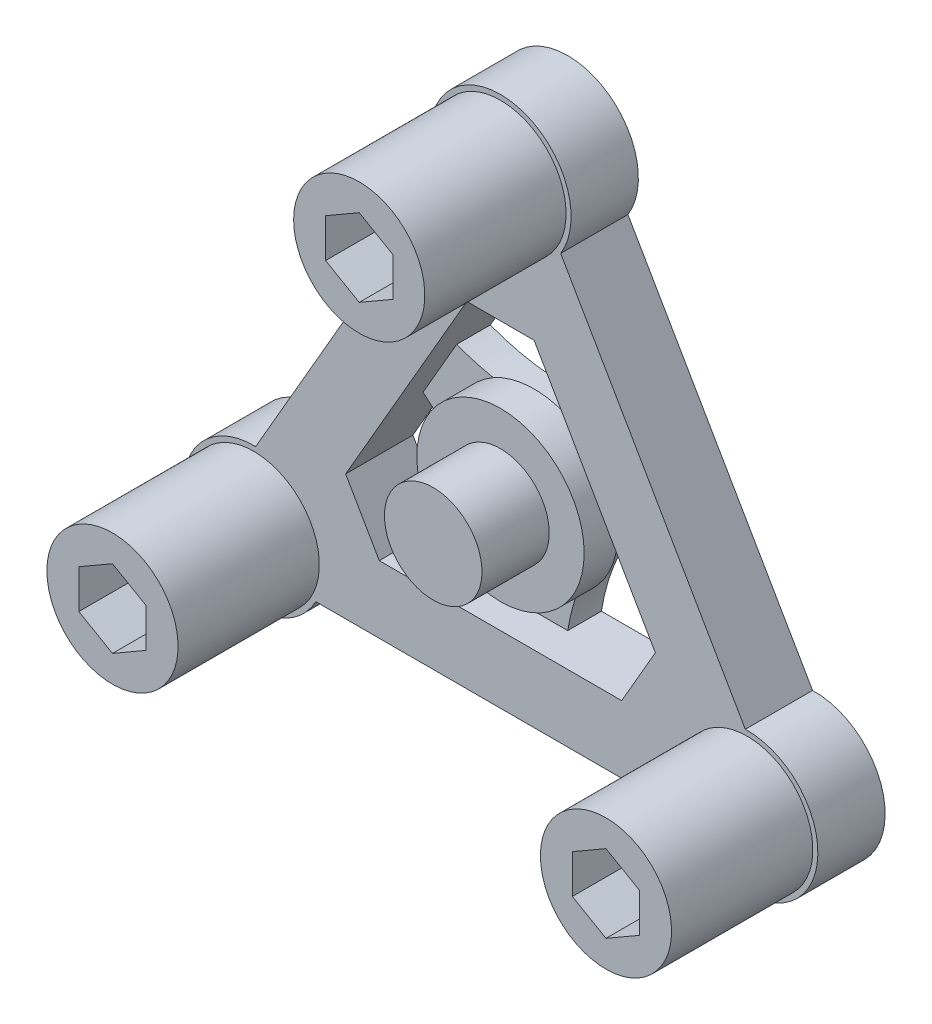
SolidWorks part; units mm, degrees
note: The reader was unsure of these and kept them because the rebuilt part matched: shared geometry of "Sketch5<3>".
ref_plane "Front Plane" through (0, 0, 0) normal (0, 0, 1) x (1, 0, 0)
ref_plane "Top Plane" through (0, 0, 0) normal (0, 1, 0) x (1, 0, 0)
ref_plane "Right Plane" through (0, 0, 0) normal (1, 0, 0) x (0, 0, -1)
sketch "Sketch1" plane through (0, 0, 0) normal (0, 0, 1) x (1, 0, 0)
  line L0 (0, 21.1785) -> (0, 0) construction
  line L1 (0, 0) -> (18.3411, -10.5892) construction
  line L2 (0, 0) -> (-18.3411, -10.5892) construction
  line L3 (0, 21.1785) -> (0, 42.357) construction
  line L4 (0, -55) -> (0, 55) construction
  line L5 (18.3411, -10.5892) -> (36.6822, -21.1785) construction
  line L6 (-18.3411, -10.5892) -> (-36.6822, -21.1785) construction
  circle A0 centre (0, 0) radius 21.1785 construction
  circle A1 centre (0, 42.357) radius 21.1785 construction
  circle A2 centre (36.6822, -21.1785) radius 21.1785 construction
  circle A3 centre (-36.6822, -21.1785) radius 21.1785 construction
  dimension "D3" = 42.357
  dimension "D4" = 42.357
  dimension "D1" = 120
  dimension "D2" = 120
sketch "Sketch2" plane through (0, 0, 0) normal (0, 0, 1) x (1, 0, 0)
  line L0 (-36.6822, -21.1785) -> (0, 42.357) construction
  line L1 (0, 42.357) -> (36.6822, -21.1785) construction
  line L2 (36.6822, -21.1785) -> (-36.6822, -21.1785) construction
  line L4 (-45.3425, -26.1785) -> (0, 52.357)
  line L7 (0, 32.357) -> (-28.022, -16.1785)
  line L8 (0, 21.1785) -> (0, 42.357) construction
  line L9 (0, 32.357) -> (28.022, -16.1785)
  line L10 (18.3411, -10.5892) -> (36.6822, -21.1785) construction
  line L11 (28.022, -16.1785) -> (-28.022, -16.1785)
  line L12 (-18.3411, -10.5892) -> (-36.6822, -21.1785) construction
  line L13 (0, -55) -> (0, 55) construction
  line L14 (0, 52.357) -> (45.3425, -26.1785)
  line L15 (45.3425, -26.1785) -> (-45.3425, -26.1785)
  line L16 (-22.6712, 13.0893) -> (-14.011, 8.0893) construction
  circle A3 centre (0, 42.357) radius 10.5
  circle A4 centre (36.6822, -21.1785) radius 10.5
  circle A5 centre (-36.6822, -21.1785) radius 10.5
  point P23 (-18.3411, 10.5893)
  point P24 (-18.3411, 10.5893)
  dimension "D2" = 21
  dimension "D1" = 10
extrude "Boss-Extrude1" add sketch "Sketch2" along normal mid plane 10 contours L4 A5 L15 | L14 A3 L4 | L15 A4 L14 | L9 A4 L11 | L11 A5 L7 | L7 A3 L9
sketch "Sketch3" plane through (0, 0, 0) normal (0, 0, 1) x (1, 0, 0)
  line L0 (-14.011, 8.0893) -> (0, 0) construction
  line L1 (28.022, -16.1785) -> (-28.022, -16.1785) construction
  line L2 (0, 0) -> (0, -16.1785) construction
  line L4 (0, 0) -> (14.011, 8.0893) construction
  line L6 (-16.511, 3.7591) -> (-11.511, 12.4194)
  line L7 (11.511, 12.4194) -> (16.511, 3.7591)
  line L8 (-5, -16.1785) -> (5, -16.1785)
  line L9 (0, 32.357) -> (28.022, -16.1785) construction
  line L10 (0, 32.357) -> (-28.022, -16.1785) construction
  arc A0 (-16.511, 3.7591) -> (-5, -16.1785) centre (-36.6822, -21.1785) cw
  arc A1 (5, -16.1785) -> (16.511, 3.7591) centre (36.6822, -21.1785) cw
  arc A2 (-11.511, 12.4194) -> (11.511, 12.4194) centre (0, 42.357) ccw
  point P14 (-14.011, 8.0893)
  point P17 (14.011, 8.0893)
  point P20 (0, -16.1785)
  dimension "D1" = 10
extrude "Boss-Extrude2" add sketch "Sketch3" against normal up to surface (5 mm away) up to face at (0, 0, -5)
sketch "Sketch4" plane through (0, 0, 5) normal (0, 0, 1) x (1, 0, 0)
  circle A0 centre (-36.6822, -21.1785) radius 9.75
  circle A1 centre (36.6822, -21.1785) radius 9.75
  circle A2 centre (0, 42.357) radius 9.75
  dimension "D1" = 19.5
extrude "Boss-Extrude3" add sketch "Sketch4" along normal blind 21
sketch "Sketch5" plane through (0, 0, 0) normal (0, 0, 1) x (1, 0, 0)
  circle A0 centre (0, 0) radius 7.25
  circle A1 centre (0, 0) radius 12.4416
  dimension "D1" = 14.5
extrude "Boss-Extrude4" add sketch "Sketch5" along normal up to surface (5 mm away) contours A1 up to face at (9.75, 42.357, 5)
extrude "Boss-Extrude5" add sketch "Sketch5<3>" along normal offset from surface (15 mm away) 10 contours A0 up to face at (12.4416, 0, 5) offset beyond the face yes
sketch "Sketch5<3>" plane through (0, 0, 0) normal (0, 0, 1) x (1, 0, 0) same geometry as "Sketch5"
chamfer "Chamfer1" distance 10 3 edges at (0, 32.357, 0) (-28.022, -16.1785, 0) (28.022, -16.1785, 0)
sketch "Sketch8" plane through (0, 0, 26) normal (0, 0, 1) x (1, 0, 0)
  line L1 (-41.6822, -24.0653) -> (-36.6822, -26.952)
  line L2 (-36.6822, -26.952) -> (-31.6822, -24.0653)
  line L3 (-31.6822, -24.0653) -> (-31.6822, -18.2917)
  line L4 (-31.6822, -18.2917) -> (-36.6822, -15.405)
  line L5 (-36.6822, -15.405) -> (-41.6822, -18.2917)
  line L6 (-41.6822, -18.2917) -> (-41.6822, -24.0653)
  line L7 (41.6822, -24.0653) -> (41.6822, -18.2917)
  line L8 (41.6822, -18.2917) -> (36.6822, -15.405)
  line L9 (36.6822, -15.405) -> (31.6822, -18.2917)
  line L10 (31.6822, -18.2917) -> (31.6822, -24.0653)
  line L11 (31.6822, -24.0653) -> (36.6822, -26.952)
  line L12 (36.6822, -26.952) -> (41.6822, -24.0653)
  line L13 (0, 48.1305) -> (-5, 45.2438)
  line L14 (-5, 45.2438) -> (-5, 39.4702)
  line L15 (-5, 39.4702) -> (0, 36.5835)
  line L16 (0, 36.5835) -> (5, 39.4702)
  line L17 (5, 39.4702) -> (5, 45.2438)
  line L18 (5, 45.2438) -> (0, 48.1305)
  circle A0 centre (-36.6822, -21.1785) radius 5 construction
  circle A1 centre (36.6822, -21.1785) radius 5 construction
  circle A2 centre (0, 42.357) radius 5 construction
  dimension "D1" = 10
extrude "Cut-Extrude1" cut sketch "Sketch8" against normal blind 10
equation "\"sN\"= 12'Sun teeth"
equation "\"rN\"= 36'Ring teeth"
equation "\"pN\"= ( \"rN\" - \"sN\" ) / 2'Planet teeth"
equation "\"m\"= 3.5'Modulus"
equation "\"sRD\"= \"sN\" * \"m\"'Sun root diam"
equation "\"rRD\"= \"rN\" * \"m\"'Ring root diam"
equation "\"pRD\"= \"pN\" * \"m\"'Planet root diam"
equation "\"D3@Sketch1\"=\"sRD\"*\"sF\""
equation "\"D4@Sketch1\"=\"pRD\"*\"sF\""
equation "\"D2@Sketch2\"=\"pRD\"*0.5"
equation "\"sF\" = 1.0085"
